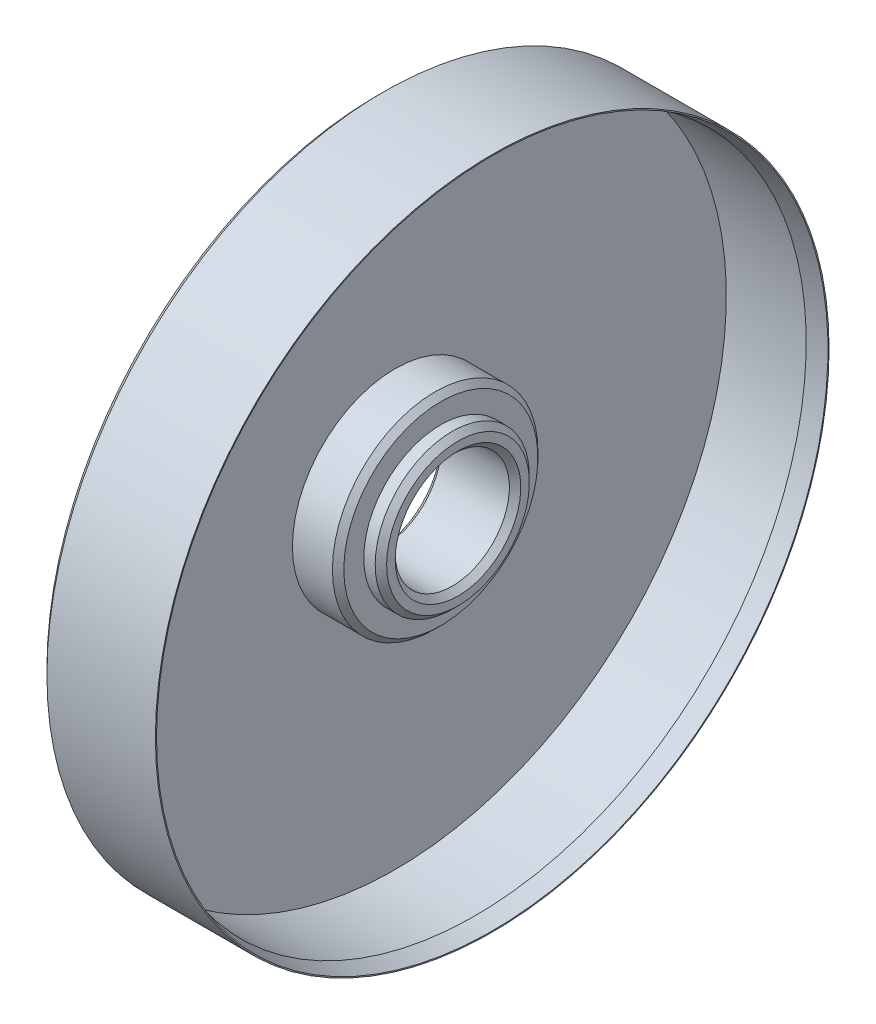
SolidWorks part; units mm, degrees
ref_plane "Спереди" through (0, 0, 0) normal (0, 0, 1) x (1, 0, 0)
ref_plane "Сверху" through (0, 0, 0) normal (0, 1, 0) x (1, 0, 0)
ref_plane "Справа" through (0, 0, 0) normal (1, 0, 0) x (0, 0, -1)
other "Configuration Table"
sketch "Эскиз1" plane through (0, 0, 0) normal (0, 0, 1) x (1, 0, 0)
  line L0 (0, 0) -> (36, 0) construction
  line L1 (0, 11) -> (0, 58)
  line L2 (1, 59) -> (20, 59)
  line L3 (20, 59) -> (20, 58.8038)
  line L4 (20, 58.8038) -> (17, 58)
  line L5 (17, 58) -> (3, 58)
  line L6 (3, 58) -> (3, 18)
  line L7 (11, 13.5) -> (13, 13.5)
  line L8 (14, 12.5) -> (14, 11)
  line L9 (13, 10) -> (1, 10)
  line L10 (3, 18) -> (10, 18)
  line L11 (11, 17) -> (11, 13.5)
  line L12 (1, 10) -> (0, 11)
  line L13 (14, 11) -> (13, 10)
  line L14 (13, 13.5) -> (14, 12.5)
  line L15 (10, 18) -> (11, 17)
  line L16 (0, 58) -> (1, 59)
  point P3 (0, 10)
  point P4 (0, 59)
  point P11 (14, 13.5)
  point P12 (14, 10)
  point P13 (11, 18)
  dimension "D1" = 20
  dimension "D2" = 14
  dimension "D3" = 3
  dimension "D4" = 27
  dimension "D5" = 8
  dimension "D6" = 36
  dimension "D7" = 20
  dimension "D8" = 15
  dimension "D9" = 1
  dimension "D10" = 118
  dimension "D11" = 3
revolve "Повернуть1" add sketch "Эскиз1" angle 360 about L0
